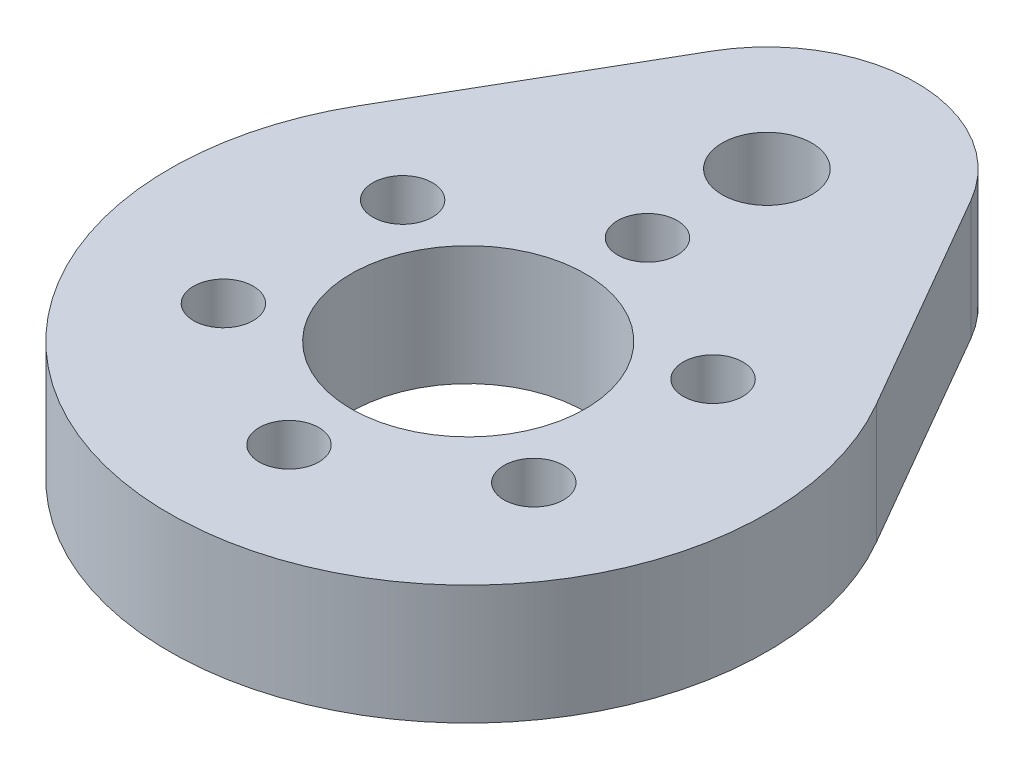
SolidWorks part; units mm, degrees
ref_plane "Front Plane" through (0, 0, 0) normal (0, 0, 1) x (1, 0, 0)
ref_plane "Top Plane" through (0, 0, 0) normal (0, 1, 0) x (1, 0, 0)
ref_plane "Right Plane" through (0, 0, 0) normal (1, 0, 0) x (0, 0, -1)
sketch "Sketch1" plane through (0, 0, 0) normal (0, 1, 0) x (1, 0, 0)
  line L0 (-5.4993, 15.875) -> (-10.9985, 6.35)
  line L1 (5.4993, 15.875) -> (10.9985, 6.35)
  line L2 (0, 0) -> (0, 12.7) construction
  arc A0 (-10.9985, 6.35) -> (10.9985, 6.35) centre (0, 0) ccw
  circle A1 centre (0, 0) radius 4.9792
  circle A2 centre (0, 7.62) radius 1.27
  circle A3 centre (6.5991, 3.81) radius 1.27
  circle A4 centre (6.5991, -3.81) radius 1.27
  circle A5 centre (0, -7.62) radius 1.27
  circle A6 centre (-6.5991, -3.81) radius 1.27
  circle A7 centre (-6.5991, 3.81) radius 1.27
  circle A8 centre (0, 12.7) radius 1.905
  arc A9 (5.4993, 15.875) -> (-5.4993, 15.875) centre (0, 12.7) ccw
  circle A10 centre (0, 0) radius 7.62 construction
  point P18 (0, 0)
  dimension "D3" = 3.81
  dimension "D4" = 6.35
  dimension "D5" = 12.7
  dimension "D6" = 15.24
  dimension "D7" = 2.54
  dimension "D2" = 12.7
  dimension "D1" = 6
extrude "Boss-Extrude1" add sketch "Sketch1" along normal blind 5.08
ref_point "Point1"
